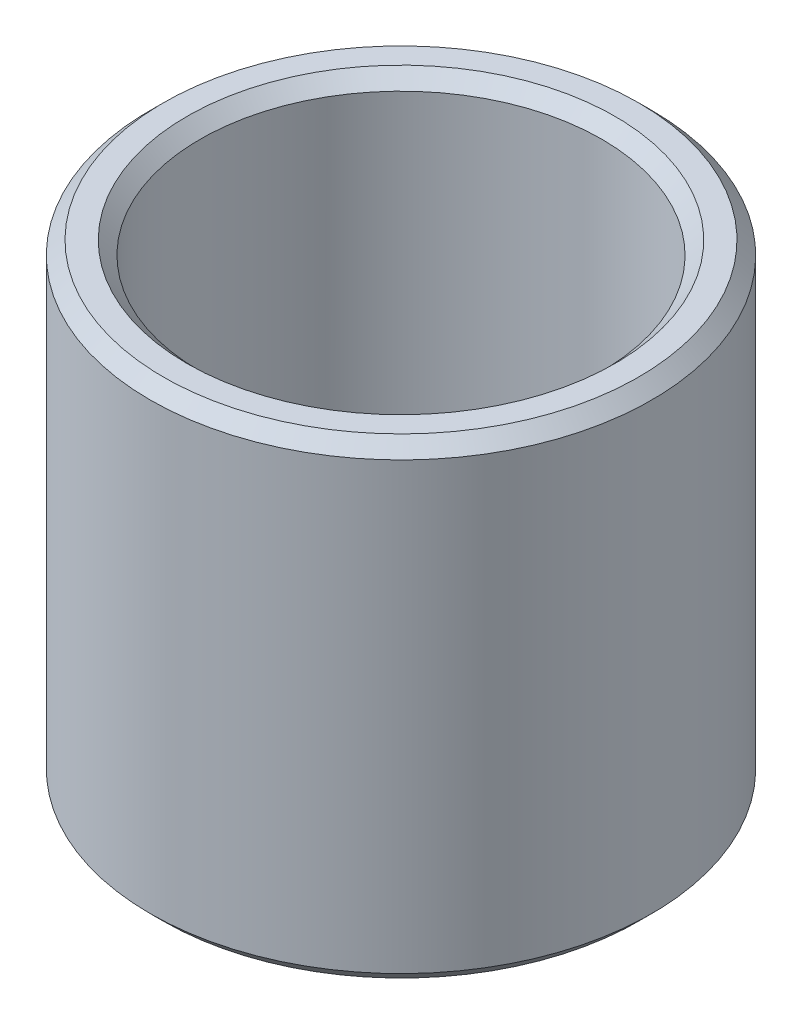
SolidWorks part; units mm, degrees
ref_plane "Front Plane" through (0, 0, 0) normal (0, 0, 1) x (1, 0, 0)
ref_plane "Top Plane" through (0, 0, 0) normal (0, 1, 0) x (1, 0, 0)
ref_plane "Right Plane" through (0, 0, 0) normal (1, 0, 0) x (0, 0, -1)
sketch "Sketch1" plane through (0, 0, 0) normal (0, 1, 0) x (1, 0, 0)
  circle A0 centre (0, 0) radius 60
  dimension "SLEEVE_OD" = 120
extrude "Boss-Extrude1" add sketch "Sketch1" along normal blind 112.7325
sketch "Sketch2" plane through (0, 0, 0) normal (0, 1, 0) x (1, 0, 0)
  circle A0 centre (0, 0) radius 48.0543
  dimension "BORE_D" = 96.1087
extrude "Cut-Extrude1" cut sketch "Sketch2" along normal through all
chamfer "Chamfer1" distance 3.1594 angle 45 4 edges at (0, 112.7325, 48.0543) (0, 0, 48.0543) (0, 0, 60) (0, 112.7325, 60)
